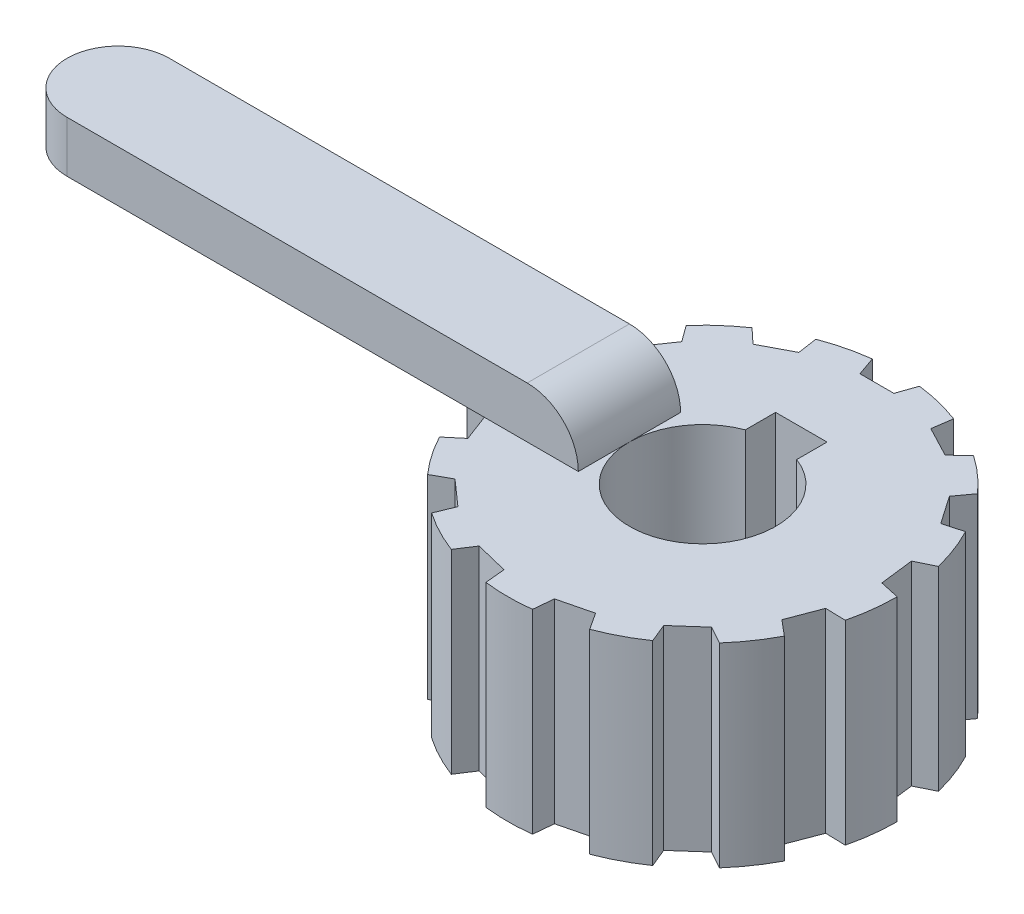
SolidWorks part; units mm, degrees
ref_plane "Front Plane" through (0, 0, 0) normal (0, 0, 1) x (1, 0, 0)
ref_plane "Top Plane" through (0, 0, 0) normal (0, 1, 0) x (1, 0, 0)
ref_plane "Right Plane" through (0, 0, 0) normal (1, 0, 0) x (0, 0, -1)
sketch "Sketch5" plane through (0, 0, 0) normal (0, 1, 0) x (1, 0, 0)
  circle A0 centre (0, 0) radius 19.05
extrude "Boss-Extrude2" add sketch "Sketch5" along normal blind 19.05
sketch "Sketch8" plane through (0, 19.05, 0) normal (0, 1, 0) x (1, 0, 0)
  line L0 (0, 19.05) -> (2.36, 19.05)
  line L1 (0, 19.05) -> (-2.36, 19.05)
  line L5 (0, 17.05) -> (-1.66, 17.05)
  line L6 (0, 17.05) -> (1.66, 17.05)
  line L7 (-2.36, 19.05) -> (-1.66, 17.05)
  line L8 (2.36, 19.05) -> (1.66, 17.05)
  circle A0 centre (0, 0) radius 19.05 construction
  point P0 (0, 19.05)
  dimension "D1" = 1.66
  dimension "D2" = 1.66
  dimension "D3" = 2
  dimension "D4" = 2.36
  dimension "D5" = 2.36
extrude "Cut-Extrude1" cut sketch "Sketch8" against normal blind 22.05
pattern_circular "CirPattern1" count 13 over 360 about axis through (0, 19.05, 0) along (0, 1, 0) of "Cut-Extrude1"
sketch "Sketch9" plane through (0, 19.05, 0) normal (0, 1, 0) x (1, 0, 0)
  line L0 (0, 7.15) -> (2.5148, 7.15)
  line L1 (0, 7.15) -> (-2.5148, 7.15)
  line L2 (-2.5148, 7.15) -> (-2.5148, 6.6931)
  line L3 (2.5148, 7.15) -> (2.5148, 6.6931)
  line L4 (-2.5148, 7.15) -> (-2.5148, 9.6564)
  line L5 (-2.5148, 9.6564) -> (2.5148, 9.6564)
  line L6 (2.5148, 9.6564) -> (2.5148, 7.15)
  circle A0 centre (0, 0) radius 7.15
extrude "Cut-Extrude2" cut sketch "Sketch9" against normal blind 25.4 contours A0 | L6 L5 L4 L1 L0 | A0 L1 L2 | A0 L3 L0 region at (0, 19.05, -8.4032) region at (-1.8902, 19.05, -7.0137) region at (1.8902, 19.05, -7.0137) region at (0, 19.05, 0)
sketch "Sketch10" plane through (0, 19.05, 0) normal (0, 1, 0) x (1, 0, 0)
  line L7 (-7.15, 0) -> (-7.15, 5)
  line L8 (-7.15, 0) -> (-7.15, -5)
  line L9 (-7.15, 5) -> (-57.15, 5)
  line L10 (-57.15, 5) -> (-57.15, -5)
  line L11 (-57.15, -5) -> (-7.15, -5)
  arc A2 (-57.15, 5) -> (-57.15, -5) centre (-57.15, 0) ccw
  arc A3 (-2.5148, 6.6931) -> (2.5148, 6.6931) centre (0, 0) ccw construction
  dimension "D1" = 50
  dimension "D2" = 5
  dimension "D3" = 5
extrude "Boss-Extrude4" add sketch "Sketch10" along normal blind 5 contours L10 A2 | L10 L11 L8 L7 L9 region at (-32.15, 19.05, 0) region at (-59.2721, 19.05, 0)
fillet "Fillet2" radius 5 1 edges at (-7.15, 24.05, 0)
